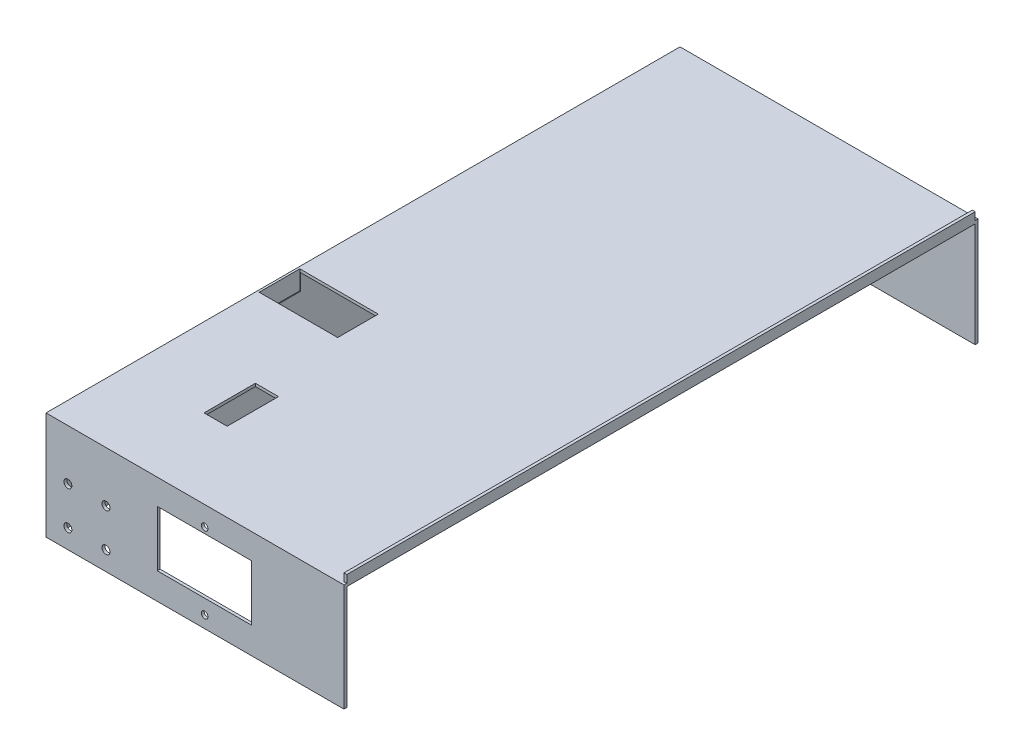
SolidWorks part; units mm, degrees
ref_plane "Front Plane" through (0, 0, 0) normal (0, 0, 1) x (1, 0, 0)
ref_plane "Top Plane" through (0, 0, 0) normal (0, 1, 0) x (1, 0, 0)
ref_plane "Right Plane" through (0, 0, 0) normal (1, 0, 0) x (0, 0, -1)
sketch "Sketch4" plane through (0, 0, 0) normal (0, 1, 0) x (1, 0, 0)
  line L0 (189.3737, 330) -> (344.3737, 330)
  line L1 (344.3737, 330) -> (344.3737, 0)
  line L2 (344.3737, 0) -> (189.3737, 0)
  line L3 (189.3737, 0) -> (189.3737, 65)
  line L7 (189.3737, 130) -> (189.3737, 330)
  line L8 (189.3737, 130) -> (189.3737, 65)
  line L10 (229.3737, 40) -> (241.5168, 40)
  line L11 (229.3737, 40) -> (229.3737, 66.9752)
  line L12 (229.3737, 66.9752) -> (241.5168, 66.9752)
  line L13 (241.5168, 40) -> (241.5168, 66.9752)
  dimension "D2" = 200
  dimension "D5" = 155
  dimension "D6" = 155
extrude "Boss-Extrude4" add sketch "Sketch4" along normal blind 1.5 separate body
sketch "Sketch5" plane through (0, 0, 0) normal (0, 0, 1) x (1, 0, 0)
  line L1 (189.3737, 1.5) -> (344.3737, 1.5)
  line L2 (189.3737, 1.5) -> (189.3737, -55)
  line L3 (189.3737, -55) -> (344.3737, -55)
  line L4 (344.3737, 1.5) -> (344.3737, -55)
  dimension "D1" = 56.5
sketch "Sketch7" plane through (0, 0, -330) normal (0, 0, -1) x (-1, 0, 0)
  line L1 (-189.3737, 1.5) -> (-344.3737, 1.5)
  line L2 (-189.3737, 1.5) -> (-189.3737, -55)
  line L3 (-189.3737, -55) -> (-344.3737, -55)
  line L4 (-344.3737, 1.5) -> (-344.3737, -55)
  dimension "D1" = 56.5
sketch "Sketch8" plane through (0, 1.5, 0) normal (0, 1, 0) x (1, 0, 0)
  line L0 (189.3737, 330) -> (344.3737, 330) construction
  line L1 (344.3737, 0) -> (342.8737, 0)
  line L2 (344.3737, 0) -> (344.3737, 330)
  line L3 (344.3737, 330) -> (342.8737, 330)
  line L4 (342.8737, 0) -> (342.8737, 330)
  dimension "D1" = 1.5
extrude "Boss-Extrude5" add sketch "Sketch5" along normal blind 1.5
extrude "Boss-Extrude14" add sketch "Sketch8" along normal blind 4
extrude "Boss-Extrude18" add sketch "Sketch7" along normal blind 1.5
sketch "Sketch9" plane through (189.3737, 0, 0) normal (-1, 0, 0) x (0, 0, 1)
  line L1 (-331.5, 1.5) -> (1.5, 1.5)
  line L2 (-331.5, 1.5) -> (-331.5, -55)
  line L3 (-331.5, -55) -> (1.5, -55)
  line L4 (1.5, 1.5) -> (1.5, -55)
extrude "Boss-Extrude19" add sketch "Sketch9" along normal blind 1.5
sketch "Sketch10" plane through (0, 0, 1.5) normal (0, 0, 1) x (1, 0, 0)
  circle A0 centre (219.3737, -45) radius 2.1
sketch "Sketch11" plane through (0, 0, 1.5) normal (0, 0, 1) x (1, 0, 0)
  circle A0 centre (199.3737, -45) radius 2.1
sketch "Sketch12" plane through (0, 0, 1.5) normal (0, 0, 1) x (1, 0, 0)
  circle A0 centre (199.3737, -25) radius 2.1
sketch "Sketch14" plane through (0, 0, 1.5) normal (0, 0, 1) x (1, 0, 0)
  circle A0 centre (219.3737, -25) radius 2.1
sketch "Sketch15" plane through (0, 0, -331.5) normal (0, 0, -1) x (-1, 0, 0)
  circle A0 centre (-219.3737, -25) radius 2.1
  circle A1 centre (-199.3737, -25) radius 2.1
  circle A2 centre (-219.3737, -45) radius 2.1
  circle A3 centre (-199.3737, -45) radius 2.1
extrude "Cut-Extrude1" cut sketch "Sketch15" against normal blind 10
extrude "Cut-Extrude2" cut sketch "Sketch14" against normal blind 10
extrude "Cut-Extrude3" cut sketch "Sketch12" against normal blind 10
extrude "Cut-Extrude4" cut sketch "Sketch10" against normal blind 10
extrude "Cut-Extrude5" cut sketch "Sketch11" against normal blind 10
sketch "Sketch17" plane through (0, 1.5, 0) normal (0, 1, 0) x (1, 0, 0)
  line L1 (188.9783, 130.6876) -> (230.1918, 130.6876)
  line L2 (188.9783, 130.6876) -> (188.9783, 109.3583)
  line L3 (188.9783, 109.3583) -> (230.1918, 109.3583)
  line L4 (230.1918, 130.6876) -> (230.1918, 109.3583)
extrude "Cut-Extrude6" cut sketch "Sketch17" against normal blind 10
sketch "Sketch18" plane through (0, 0, 1.5) normal (0, 0, 1) x (1, 0, 0)
  line L1 (246.3048, -11.7715) -> (295.8862, -11.7715)
  line L2 (246.3048, -11.7715) -> (246.3048, -41.091)
  line L3 (246.3048, -41.091) -> (295.8862, -41.091)
  line L4 (295.8862, -11.7715) -> (295.8862, -41.091)
sketch "Sketch19" plane through (0, 0, 1.5) normal (0, 0, 1) x (1, 0, 0)
  circle A0 centre (271.1965, -8.7391) radius 1.75
  circle A1 centre (271.1965, -48.7391) radius 1.75
extrude "Cut-Extrude7" cut sketch "Sketch18" against normal blind 10
extrude "Cut-Extrude8" cut sketch "Sketch19" against normal blind 10
